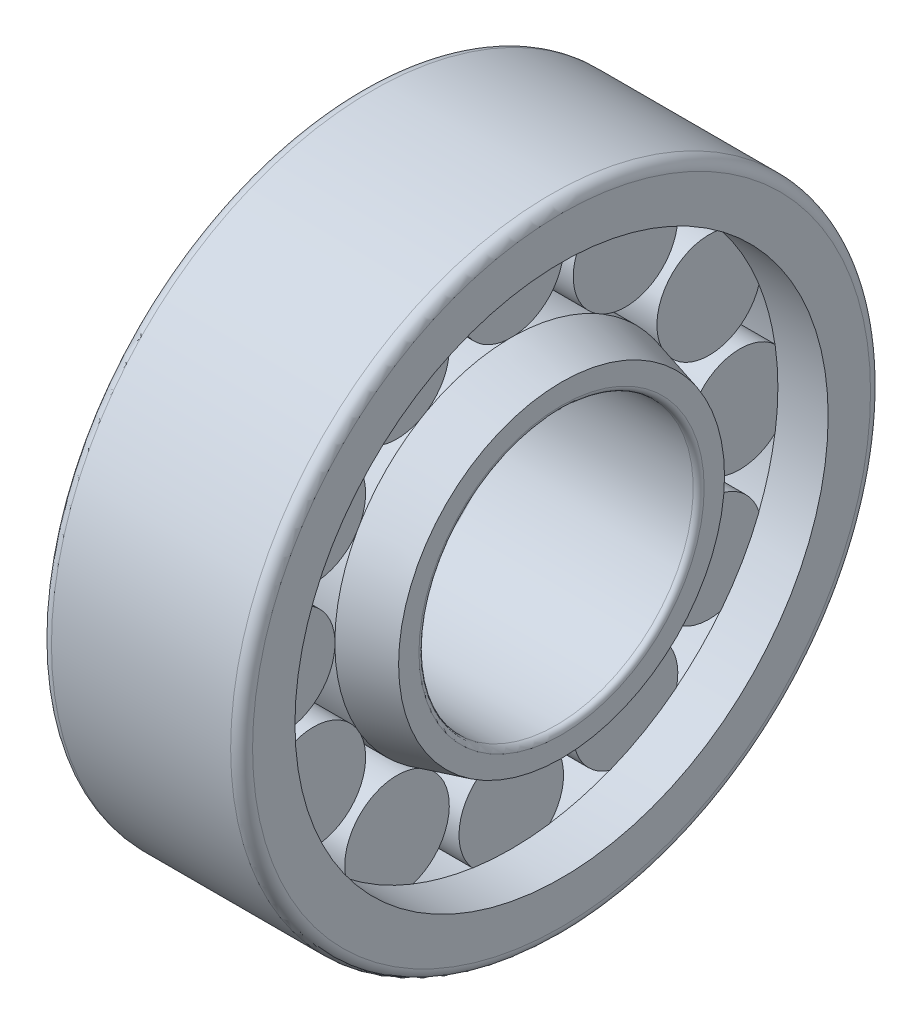
SolidWorks part; units mm, degrees
ref_plane "Front" through (0, 0, 0) normal (0, 0, 1) x (1, 0, 0)
ref_plane "Top" through (0, 0, 0) normal (0, 1, 0) x (1, 0, 0)
ref_plane "Right" through (0, 0, 0) normal (1, 0, 0) x (0, 0, -1)
sketch "Sketch1" plane through (0, 0, 0) normal (0, 0, 1) x (1, 0, 0)
  line L0 (-5.5, 7.5) -> (5.5, 7.5)
  line L1 (5.5, 7.5) -> (5.5, 8.9131)
  line L2 (5.5, 8.9131) -> (2.75, 9.65)
  line L3 (2.75, 9.65) -> (-2.75, 9.65)
  line L4 (-2.75, 9.65) -> (-5.5, 8.9131)
  line L5 (-5.5, 8.9131) -> (-5.5, 7.5)
  line L6 (-10.1379, 0) -> (10.5422, 0) construction
  dimension "D5" = 15
  dimension "D6" = 15
  dimension "D7" = 5.5
  dimension "D2" = 5.5
  dimension "D8" = 2.75
  dimension "B" = 11
revolve "Revolve1" add sketch "Sketch1" angle 360 about L6
sketch "Sketch2" plane through (0, 0, 0) normal (0, 0, 1) x (1, 0, 0)
  line L0 (-2.75, 9.64) -> (2.75, 9.64)
  line L1 (2.75, 9.64) -> (2.75, 12.5)
  line L2 (-2.75, 12.5) -> (2.75, 12.5)
  line L3 (-2.75, 12.5) -> (-2.75, 9.64)
  line L4 (-7.1198, 0) -> (7.769, 0) construction
  line L6 (-7.4228, 12.5) -> (7.769, 12.5) construction
  dimension "D1" = 19.28
  dimension "D2" = 12.5
  dimension "D4" = 5.5
  dimension "D5" = 2.75
revolve "Revolve2" add sketch "Sketch2" angle 360 about L6
sketch "Sketch3" plane through (0, 0, 0) normal (0, 0, 1) x (1, 0, 0)
  line L0 (-5.5, 17.5) -> (5.5, 17.5)
  line L1 (5.5, 17.5) -> (5.5, 14.5825)
  line L2 (5.5, 14.5825) -> (2.74, 14.5825)
  line L3 (2.74, 14.5825) -> (2.74, 15.35)
  line L4 (2.74, 15.35) -> (-2.74, 15.35)
  line L5 (-2.74, 15.35) -> (-2.74, 14.5825)
  line L6 (-2.74, 14.5825) -> (-5.5, 14.5825)
  line L7 (-5.5, 14.5825) -> (-5.5, 17.5)
  line L8 (-9.0822, 0) -> (10.5352, 0) construction
  dimension "D2" = 30.7
  dimension "D3" = 29.165
  dimension "B" = 11
  dimension "D6" = 5.48
  dimension "D7" = 2.74
  dimension "D5" = 5.5
revolve "Revolve3" add sketch "Sketch3" angle 360 about L8
pattern_circular "Circular-Pattern1" count 12 over 360 about axis through (-10.1379, 0, 0) along (1, 0, 0) of "Revolve2"
fillet "Fillet1" radius 0.6 2 edges at (-5.5, 0, 17.5) (5.5, 0, 17.5)
fillet "Fillet2" radius 0.3 2 edges at (5.5, 0, 7.5) (-5.5, 0, 7.5)
equation "\"D2@Sketch1\" = \"B@Sketch1\" / 2"
equation "\"D7@Sketch1\" = \"D2@Sketch1\""
equation "\"D8@Sketch1\" = \"D7@Sketch1\"/2"
equation "\"D2@Sketch2\" = ( \"DD@Sketch3\" + \"d@Sketch1\" )  / 4"
equation "\"D4@Sketch2\" = \"B@Sketch1\" / 2"
equation "\"D5@Sketch2\" = \"D4@Sketch2\" / 2"
equation "\"D1@Sketch2\" = \"FW@Sketch1\" - 0.02"
equation "\"B@Sketch3\" = \"B@Sketch1\""
equation "\"D5@Sketch3\" = \"B@Sketch3\" / 2"
equation "\"D6@Sketch3\" = \"D5@Sketch3\" - 0.02"
equation "\"D7@Sketch3\" = \"D6@Sketch3\" / 2"
equation "\"D2@Sketch3\" = ( \"DD@Sketch3\" + \"d@Sketch1\" )  / 4 * 2 + ( ( \"DD@Sketch3\" + \"d@Sketch1\" )  / 4 * 2 - \"FW@Sketch1\"  ) "
equation "\"D3@Sketch3\" = \"D2@Sketch3\" * 0.95"
equation "\"m@Circular-Pattern1\"=int(3.14159265/atn(((\"DD@Sketch3\"+\"d@Sketch1\")/4-\"FW@Sketch1\"/2+0.02) / sqr((\"DD@Sketch3\"+\"d@Sketch1\")/4  * (\"DD@Sketch3\"+\"d@Sketch1\")/4 - ((\"DD@Sketch3\"+\"d@Sketch1\")/4-\"FW@Sketch1\"/2+0.02) *  ((\"DD@Sketch3\"+\"d@Sketch1\")/4-\"FW@Sketch1\"/2+0.02))))-1"
